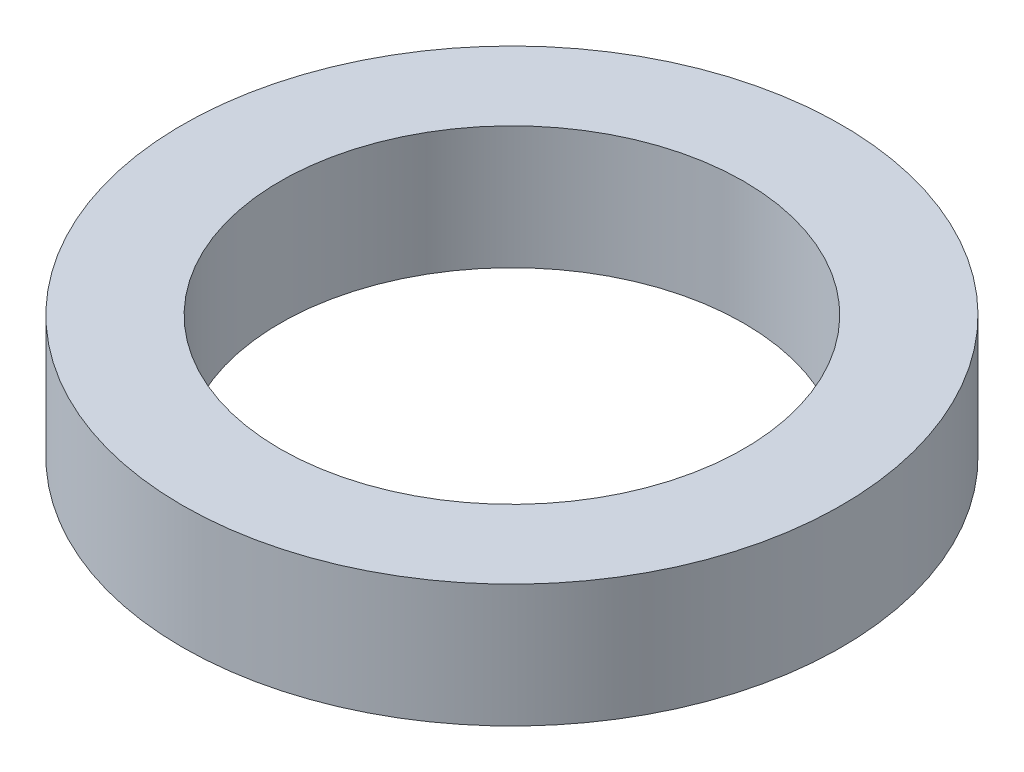
SolidWorks part; units mm, degrees
ref_plane "Front Plane" through (0, 0, 0) normal (0, 0, 1) x (1, 0, 0)
ref_plane "Top Plane" through (0, 0, 0) normal (0, 1, 0) x (1, 0, 0)
ref_plane "Right Plane" through (0, 0, 0) normal (1, 0, 0) x (0, 0, -1)
sketch "Sketch1" plane through (0, 0, 0) normal (0, 1, 0) x (1, 0, 0)
  circle A0 centre (0, 0) radius 5.2705
  circle A1 centre (0, 0) radius 7.493
  dimension "D2" = 14.986
  dimension "D1" = 10.541
extrude "Boss-Extrude1" add sketch "Sketch1" along normal blind 2.794
